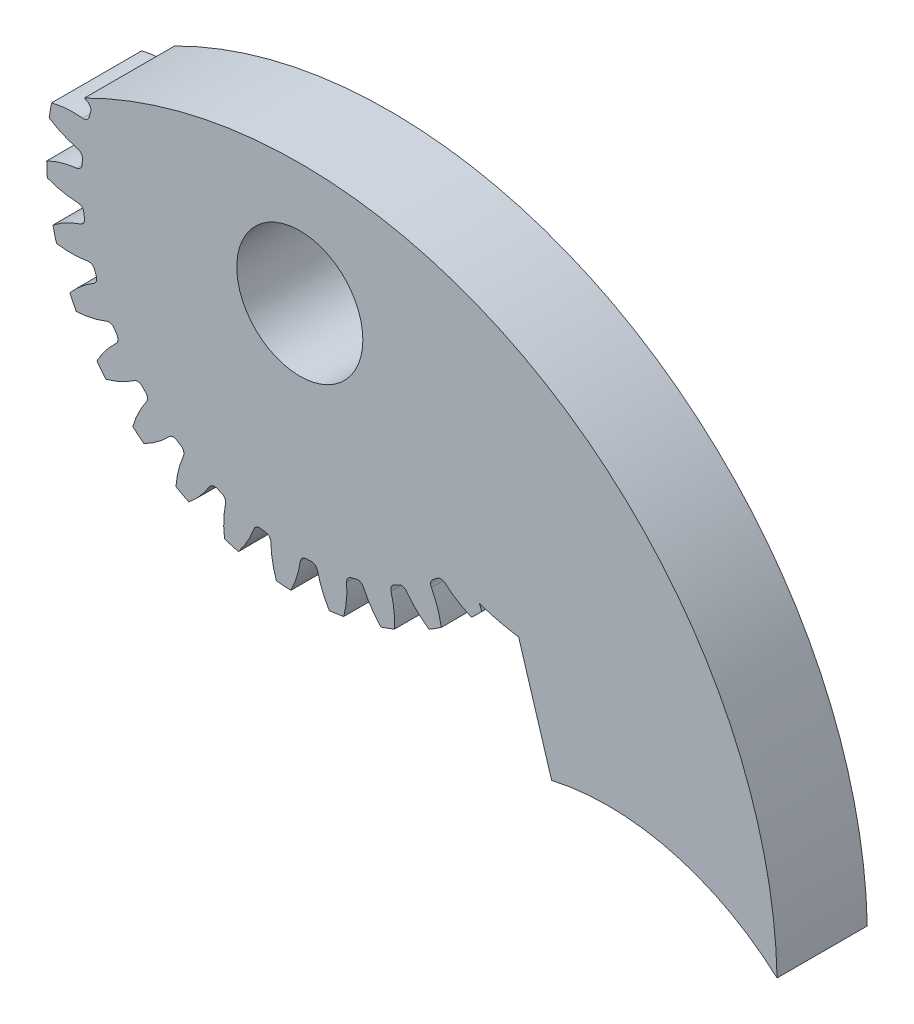
SolidWorks part; units mm, degrees
material "ABS"
ref_plane "Front" through (0, 0, 0) normal (0, 0, 1) x (1, 0, 0)
ref_plane "Top" through (0, 0, 0) normal (0, 1, 0) x (1, 0, 0)
ref_plane "Right" through (0, 0, 0) normal (1, 0, 0) x (0, 0, -1)
sketch "Sketch3" plane through (0, 0, 0) normal (0, 0, 1) x (1, 0, 0)
  circle A0 centre (0, 0) radius 40.64
  dimension "od" = 81.28
extrude "gearBody" add sketch "Sketch3" along normal blind 9.652
sketch "Sketch2" plane through (0, 0, 0) normal (0, 0, 1) x (1, 0, 0)
  line L0 (0, 0) -> (34.0786, 14.1158) construction
  line L1 (45.4751, -11.4855) -> (0, 0) construction
  line L2 (0, 0) -> (36.3143, 0) construction
  line L3 (38.0972, -0.458) -> (37.8451, -4.4001) construction
  line L5 (37.9712, -2.4291) -> (0, 0) construction
  line L7 (0, 0) -> (36.8864, 0) construction
  arc A0 (36.879, -0.7403) -> (36.6727, -3.9649) centre (0, 0) ccw construction
  arc A1 (40.637, 0.4947) -> (40.2427, -5.6687) centre (0, 0) ccw construction
  arc A2 (38.0972, -0.458) -> (37.8451, -4.4001) centre (0, 0) ccw construction
  arc A3 (34.9015, -2.6404) -> (34.9534, -1.8283) centre (0, 0) ccw
  arc A4 (45.4751, -11.4855) -> (35.6466, -3.6712) centre (32.0022, -18.3431) ccw
  arc A5 (45.4751, -11.4855) -> (46.5679, 5.5974) centre (0, 0) ccw
  arc A6 (46.5679, 5.5974) -> (35.8238, -0.9008) centre (34.0786, 14.1158) cw
  arc A7 (34.9534, -1.8283) -> (35.8238, -0.9008) centre (35.9376, -1.8798) cw
  arc A8 (35.6466, -3.6712) -> (34.9015, -2.6404) centre (35.8842, -2.7147) cw
  point P6 (46.5679, 5.5974)
  point P22 (45.4751, -11.4855)
  dimension "baseDia" = 73.7729
  dimension "od" = 81.28
  dimension "pd" = 76.2
  dimension "rd" = 70.0024
  dimension "rFillet" = 0.9855
  dimension "pointX" = 46.5679
  dimension "pointY" = 5.5974
  dimension "CTT" = 3.9421
  dimension "flankCenterAngle" = 22.5
extrude "toothCut" cut sketch "Sketch2" along normal through all
pattern_circular "CirPattern1" count 30 over 360 about axis through (0, 0, 9.652) along (0, 0, -1) of "toothCut"
scale "Scale1" scale about centroid uniform scaling no x scale factor 0.666667 y scale factor 0.666667 z scale factor 1
sketch "hub1Dia" plane through (0, 0, 0) normal (0, 0, -1) x (-1, 0, 0)
  circle A0 centre (0, 0) radius 12.7
  dimension "hub1Dia" = 25.4
sketch "hub2Dia" plane through (0, 0, 9.652) normal (0, 0, 1) x (1, 0, 0)
  circle A0 centre (0, 0) radius 12.7
  dimension "hub2dia" = 25.4
sketch "boreDia" plane through (0, 0, 0) normal (0, 0, 1) x (1, 0, 0)
  circle A0 centre (0, 0) radius 6.7469
  dimension "boreDia" = 13.4937
extrude "bore" cut sketch "boreDia" against normal mid plane 25400
sketch "Sketch4" plane through (0, 0, 9.652) normal (0, 0, 1) x (1, 0, 0)
  circle A0 centre (0, -38.1) radius 51.1048
  arc A2 (-27.9892, 4.6587) -> (27.9892, 4.6587) centre (0, 0) cw
  dimension "D1" = 102.2096
  dimension "D2" = 38.1
extrude "Cut-Extrude1" cut sketch "Sketch4" against normal through all contours A0 region at (0, 17.6405, 9.652)
sketch "Sketch5" plane through (0, 0, 9.652) normal (0, 0, 1) x (1, 0, 0)
  line L0 (0, -38.1) -> (51.1048, -38.1) construction
  line L1 (0, 0) -> (0, -38.1) construction
  line L2 (0, -38.1) -> (-25.5524, 6.1581) construction
  line L3 (0, -38.1) -> (44.2581, -63.6524) construction
  line L4 (23.4248, -19.2156) -> (26.9592, -30.742)
  circle A0 centre (0, -38.1) radius 51.1048 construction
  arc A1 (21.891, 8.0789) -> (-23.0664, 7.5031) centre (0, -38.1) ccw construction
  circle A2 centre (0, -38.1) radius 14.3933 construction
  circle A3 centre (32.9956, -57.15) radius 27.0891 construction
  arc A4 (26.9592, -30.742) -> (51.0928, -36.9929) centre (32.9956, -57.15) cw
  arc A5 (51.0928, -36.9929) -> (8.2583, 12.3331) centre (0, -38.1) ccw
  spline S0 degree 2 poles (8.2583, 12.3331) (3.9786, -16.3376) (23.4248, -19.2156) knots 0 0 0 1 1 1
  dimension "D2" = 28.7867
  dimension "D4" = 54.1782
  dimension "D1" = 120
  dimension "D3" = 120
  dimension "D5" = 38.1
extrude "Boss-Extrude1" add sketch "Sketch5" against normal up to surface (9.652 mm away) up to face at (6.7469, 0, 0)
equation "\"Aft_Section_Length\"= 30in"
equation "\"Mid_Coupler_Length\"= 12in"
equation "\"AB_Coupler_OD_Length\"= 1in"
equation "\"AB_Coupling_Section_Length\"= 0.375in"
equation "\"AB_Coupler_Length\"= \"AB_Coupler_OD_Length\" + \"AB_Coupling_Section_Length\" * 2"
equation "\"Cutout_Angle\"= 60"
equation "\"AB_Paddle_Height\"= 0.375in"
equation "\"AB_Coupler_Num_Screws\"= 4"
equation "\"Num_Cutouts\"= 4"
equation "\"AB_Coupler_OD\"= 4.024in"
equation "\"AB_Coupler_ID\"= 3.7in"
equation "\"AB_Coupler_Surface_Diameter\"= 3.899in"
equation "\"AB_Coupling_Screw_Diameter\"= 0.1065in"
equation "\"AB_Central_Bushing_Length\"= 0.75in"
equation "\"Lead_Screw_Dist\"= 2in"
equation "\"Lead_Screw_Diam\"= 0.375in"
equation "\"Lead_Screw_Length\"= \"Mid_Coupler_Length\" + 2*0.375in + 2*0.5in"
equation "\"Paddle_Pin_Offset\"= 0.25in"
equation "\"Paddle_Pin_Radius\"= 2.25*2/3in"
equation "\"Fwd_BKHD_From_Top\"= 18in"
equation "\"D1@Sketch4\" = \"Body_Tube_OD\""
equation "\"D2@Sketch4\"=\"Paddle_Pin_Radius\""
equation "\"Motor_OD\"= 54mm"
equation "\"Paddle_Gear_OD\"= 3.2in"
equation "\"Drive_Gear_OD\"= 1.7*2/3in"
equation "\"Fin_Thickness\"= 0.118in"
equation "\"DB9_Hole_Dist\"= 25mm"
equation "\"Motor_Length\"= 401mm"
equation "\"Body_Tube_OD\"= 4.024in"
equation "\"Body_Tube_ID\"= 3.90in"
equation "\"Coupler_OD\"= 3.899in"
equation "\"Coupler_ID\"= 3.755in"
equation "\"Fwd_Section_Length\"= 25in"
equation "\"Mid_Section_Length\"= 6in"
equation "\"Aft_Upper_Tube_Length\"= 10in"
equation "\"Aft_Lower_Tube_Length\"= 18in"
equation "\"Nosecone_Coupler_Length\"= 5in"
equation "\"Avionics_Bulkhead_Thickness\"= 0.25in"
equation "\"Avionics_Bulkhead_Lip\"= 0.125in"
equation "\"Avionics_Board_Length\"= \"Mid_Coupler_Length\" - 2*\"Avionics_Bulkhead_Lip\""
equation "\"Lead_Screw_Hole_Diam\"= (27/64)*1in"
equation "\"Centering_Ring_Cutout_Dia\"=1.5in"
equation "\"Airbrakes_Wire_Hole_Dist\"= 1.1in"
equation "\"Airbrakes_Wire_Hole_Dia\"= 0.25in"
equation "\"DB9_Relief_Width\"= 0.47in"
equation "\"DB9_Relief_Hole_Offset\"= 0.09in"
equation "\"Servo_Gear_Offset\"= 0.5in"
equation "\"D2@Sketch5\"=\"Drive_Gear_OD\""
equation "\"D5@Sketch5\"=\"Paddle_Pin_Radius\""
